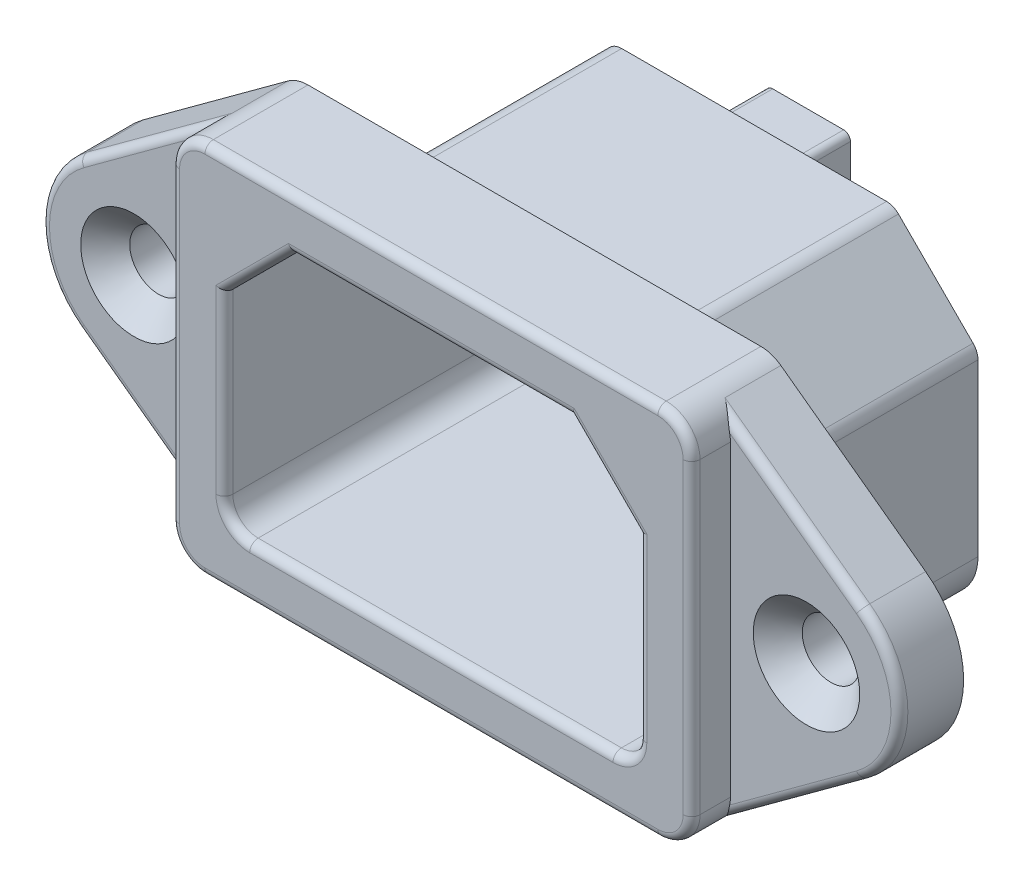
SolidWorks part; units mm, degrees
ref_plane "Спереди" through (0, 0, 0) normal (0, 0, 1) x (1, 0, 0)
ref_plane "Сверху" through (0, 0, 0) normal (0, 1, 0) x (1, 0, 0)
ref_plane "Справа" through (0, 0, 0) normal (1, 0, 0) x (0, 0, -1)
sketch "Эскиз1" plane through (0, 0, 0) normal (0, 0, 1) x (1, 0, 0)
  line L0 (-66.2816, 0) -> (64.7065, 0) construction
  line L2 (-13.4, 11.1) -> (13.4, 11.1)
  line L3 (-15.4, 9.1) -> (-15.4, -9.1)
  line L4 (-13.4, -11.1) -> (13.4, -11.1)
  line L5 (15.4, 9.1) -> (15.4, -9.1)
  arc A0 (-13.4, 11.1) -> (-15.4, 9.1) centre (-13.4, 9.1) ccw
  arc A1 (-15.4, -9.1) -> (-13.4, -11.1) centre (-13.4, -9.1) ccw
  arc A2 (13.4, -11.1) -> (15.4, -9.1) centre (13.4, -9.1) ccw
  arc A3 (15.4, 9.1) -> (13.4, 11.1) centre (13.4, 9.1) ccw
  point P11 (-15.4, 11.1)
  point P14 (-15.4, -11.1)
  point P17 (15.4, -11.1)
  dimension "D5" = 2
  dimension "D1" = 22.2
  dimension "D2" = 11.1
  dimension "D3" = 30.8
  dimension "D4" = 15.4
extrude "Бобышка-Вытянуть1" add sketch "Эскиз1" along normal blind 2.3
sketch "Эскиз2" plane through (0, 0, 0) normal (0, 0, -1) x (-1, 0, 0)
  line L0 (-32.3689, 0) -> (35.169, 0) construction
  line L1 (-23.1502, 4.4369) -> (-14.5819, 10.7134)
  line L2 (-23.1502, -4.4369) -> (-14.5819, -10.7134)
  line L4 (-15.4, -9.1) -> (-15.4, 9.1) construction
  line L5 (0, 0) -> (0, 11.1) construction
  line L6 (-13.4, 11.1) -> (13.4, 11.1) construction
  line L7 (23.1502, -4.4369) -> (14.5819, -10.7134)
  line L8 (23.1502, 4.4369) -> (14.5819, 10.7134)
  line L9 (-13.4, 11.1) -> (13.4, 11.1)
  line L10 (-13.4, -11.1) -> (13.4, -11.1)
  arc A1 (-15.4, -9.1) -> (-13.4, -11.1) centre (-13.4, -9.1) ccw construction
  arc A2 (-13.4, 11.1) -> (-15.4, 9.1) centre (-13.4, 9.1) ccw construction
  arc A3 (-23.1502, -4.4369) -> (-23.1502, 4.4369) centre (-19.9, 0) cw
  arc A4 (-14.5819, 10.7134) -> (-13.4, 11.1) centre (-13.4, 9.1) cw
  arc A5 (-14.5819, -10.7134) -> (-13.4, -11.1) centre (-13.4, -9.1) ccw
  arc A6 (14.5819, -10.7134) -> (13.4, -11.1) centre (13.4, -9.1) cw
  arc A7 (14.5819, 10.7134) -> (13.4, 11.1) centre (13.4, 9.1) ccw
  arc A8 (23.1502, -4.4369) -> (23.1502, 4.4369) centre (19.9, 0) ccw
  point P16 (-29.2072, 0)
  point P36 (29.2072, 0)
  dimension "D2" = 5.5
  dimension "D1" = 4.5
extrude "Бобышка-Вытянуть2" add sketch "Эскиз2" along normal blind 3.8
hole_wizard "Зенковка для винта с полупотайной головкой M31" positions "Эскиз4" profile "Эскиз3" countersink size "M3" standard "Din" end condition through all
sketch "Эскиз4" plane through (0, 0, 0) normal (0, 0, 1) x (1, 0, 0)
  point P0 (19.9, 0)
  point P3 (-19.9, 0)
sketch "Эскиз3" plane through (19.9, 0, 0) normal (1, 0, 0) x (0, -1, 0)
  line L0 (0, 0) -> (0, 3.8)
  line L1 (0, 3.8) -> (1.7, 3.8)
  line L2 (1.7, 3.8) -> (1.7, 1.45)
  line L3 (1.7, 1.45) -> (3.15, 0)
  line L5 (3.15, 0) -> (0, 0)
  line L6 (-1.7, 1.45) -> (-3.15, 0) construction
  line L11 (0, -6.35) -> (0, 107.95) construction
  dimension "Диаметр сквозного отверстия" = 3.4
  dimension "Глубина сквозного отверстия" = 3.8
  dimension "Диаметр передней зенковки" = 6.3
  dimension "Угол передней зенковки" = 90
sketch "Эскиз5" plane through (0, 0, -3.8) normal (0, 0, -1) x (-1, 0, 0)
  line L0 (0, 0) -> (15.8826, 0) construction
  line L1 (-8.25, 9.25) -> (8.25, 9.25)
  line L2 (-13.25, 4.25) -> (-13.25, -6.25)
  line L3 (-10.25, -9.25) -> (10.25, -9.25)
  line L4 (13.25, 4.25) -> (13.25, -6.25)
  line L5 (0, 0) -> (0, 9.9963) construction
  line L6 (8.25, 9.25) -> (13.25, 4.25)
  line L7 (-13.25, 4.25) -> (-8.25, 9.25)
  arc A0 (-13.25, -6.25) -> (-10.25, -9.25) centre (-10.25, -6.25) ccw
  arc A1 (10.25, -9.25) -> (13.25, -6.25) centre (10.25, -6.25) ccw
  point P0 (-13.25, 9.25)
  point P3 (13.25, 9.25)
  point P14 (-13.25, -9.25)
  dimension "D5" = 3
  dimension "D1" = 26.5
  dimension "D2" = 18.5
  dimension "D3" = 13.25
  dimension "D4" = 9.25
extrude "Бобышка-Вытянуть3" add sketch "Эскиз5" along normal blind 13
fillet "Скругление1" radius 1 4 edges at (13.25, 4.25, -10.3) (-13.25, 4.25, -10.3) (8.25, 9.25, -10.3) (-8.25, 9.25, -10.3)
sketch "Эскиз6" plane through (0, 0, 2.3) normal (0, 0, 1) x (1, 0, 0)
  line L0 (0, 0) -> (13.6023, 0) construction
  line L1 (-8.25, 8) -> (8.25, 8)
  line L2 (-12.25, 4) -> (-12.25, -6.5)
  line L3 (-10.75, -8) -> (10.75, -8)
  line L4 (12.25, 4) -> (12.25, -6.5)
  line L5 (0, 0) -> (0, 9.625) construction
  line L6 (8.25, 8) -> (12.25, 4)
  line L7 (-8.25, 8) -> (-12.25, 4)
  arc A0 (-12.25, -6.5) -> (-10.75, -8) centre (-10.75, -6.5) ccw
  arc A1 (12.25, -6.5) -> (10.75, -8) centre (10.75, -6.5) cw
  point P0 (-12.25, 8)
  point P3 (12.25, 8)
  point P10 (-12.25, -8)
  dimension "D5" = 1.5
  dimension "D1" = 24.5
  dimension "D2" = 16
  dimension "D3" = 8
  dimension "D4" = 12.25
extrude "Вырез-Вытянуть1" cut sketch "Эскиз6" against normal blind 17
fillet "Скругление2" radius 0.5 22 edges at (25.4, 0, 0) (-25.4, 0, 0) (-12.25, -1.25, 2.3) (-11.8107, -7.5607, 2.3) (12.25, -1.25, 2.3) (11.8107, -7.5607, 2.3) (-14.8142, -10.5142, 2.3) (-15.4, 0, 2.3) (-14.8142, 10.5142, 2.3) (0, 11.1, 2.3) (14.8142, 10.5142, 2.3) (15.4, 0, 2.3) (14.8142, -10.5142, 2.3) (10.25, 6, 2.3) (0, 8, 2.3) (-10.25, 6, 2.3) (0, -8, 2.3) (0, -11.1, 2.3)
sketch "Эскиз7" plane through (0, 0, -16.8) normal (0, 0, -1) x (-1, 0, 0)
  line L0 (0, 9.25) -> (0, -9.25) construction
  line L1 (7.8358, 9.25) -> (-7.8358, 9.25) construction
  line L2 (-10.25, -9.25) -> (10.25, -9.25) construction
  line L3 (7.8358, 9.25) -> (-7.8358, 9.25) construction
  line L4 (-2.5, 8.45) -> (2.5, 8.45)
  line L5 (-2.5, 8.45) -> (-2.5, -1.55)
  line L6 (-2.5, -1.55) -> (2.5, -1.55)
  line L7 (2.5, 8.45) -> (2.5, -1.55)
  line L8 (-9.5, 1.55) -> (-4.5, 1.55)
  line L9 (-9.5, 1.55) -> (-9.5, -8.45)
  line L10 (-9.5, -8.45) -> (-4.5, -8.45)
  line L11 (-4.5, 1.55) -> (-4.5, -8.45)
  line L12 (-10.25, -9.25) -> (10.25, -9.25) construction
  line L13 (9.5, -8.45) -> (4.5, -8.45)
  line L14 (4.5, 1.55) -> (4.5, -8.45)
  line L15 (9.5, 1.55) -> (4.5, 1.55)
  line L16 (9.5, 1.55) -> (9.5, -8.45)
  dimension "D1" = 5
  dimension "D2" = 10
  dimension "D3" = 2.5
  dimension "D4" = 0.8
  dimension "D5" = 10
  dimension "D6" = 5
  dimension "D7" = 0.8
  dimension "D8" = 9
extrude "Бобышка-Вытянуть4" add sketch "Эскиз7" along normal blind 3.2
fillet "Скругление3" radius 0.4 12 edges at (4.5, -8.45, -18.4) (9.5, -8.45, -18.4) (-9.5, -8.45, -18.4) (-4.5, -8.45, -18.4) (-2.5, -1.55, -18.4) (2.5, -1.55, -18.4) (-9.5, 1.55, -18.4) (-4.5, 1.55, -18.4) (-2.5, 8.45, -18.4) (2.5, 8.45, -18.4) (4.5, 1.55, -18.4) (9.5, 1.55, -18.4)
sketch "Эскиз8" plane through (0, 0, -16.8) normal (0, 0, -1) x (-1, 0, 0)
  line L0 (9.7426, -5.4534) -> (13.0574, -5.4534) construction
  line L1 (-12.9955, -5.4534) -> (-9.8079, -5.4534) construction
  line L2 (-3.5635, -4.7348) -> (3.5707, -4.7348) construction
  line L3 (5.6283, 7.866) -> (5.6283, 2.6401) construction
  line L4 (5.4283, 7.866) -> (5.8283, 7.866)
  line L5 (5.4283, 7.866) -> (5.4283, 5.866)
  line L6 (5.8283, 5.866) -> (7.8283, 5.866)
  line L7 (5.8283, 7.866) -> (5.8283, 5.866)
  line L8 (3.4283, 5.866) -> (5.4283, 5.866)
  line L9 (3.4283, 5.866) -> (3.4283, 5.466)
  line L10 (3.4283, 5.466) -> (7.8283, 5.466)
  line L11 (7.8283, 5.866) -> (7.8283, 5.466)
  line L12 (4.2283, 5.166) -> (7.0283, 5.166)
  line L13 (4.2283, 5.166) -> (4.2283, 4.766)
  line L14 (4.2283, 4.766) -> (7.0283, 4.766)
  line L15 (7.0283, 5.166) -> (7.0283, 4.766)
  line L16 (4.9283, 4.466) -> (6.3283, 4.466)
  line L17 (4.9283, 4.466) -> (4.9283, 4.066)
  line L18 (4.9283, 4.066) -> (6.3283, 4.066)
  line L19 (6.3283, 4.466) -> (6.3283, 4.066)
  line L20 (-6.5168, 4.066) -> (-2.7939, 4.066) construction
  text T0 "L" font "Arial" height 3
  text T1 "N" font "Arial" height 3
  text T2 "10A\r\n250V~" font "Arial" height 1.8
  text T3 "E" font "Arial" height 3
  dimension "D1" = 0.4
  dimension "D2" = 0.4
  dimension "D3" = 2
  dimension "D4" = 2
  dimension "D5" = 2
  dimension "D6" = 0.3
  dimension "D7" = 0.4
  dimension "D8" = 0.4
  dimension "D9" = 0.3
  dimension "D10" = 2.8
  dimension "D11" = 1.4
  dimension "D12" = 1.4
  dimension "D13" = 0.7
extrude "Бобышка-Вытянуть5" add sketch "Эскиз8" along normal blind 0.2
